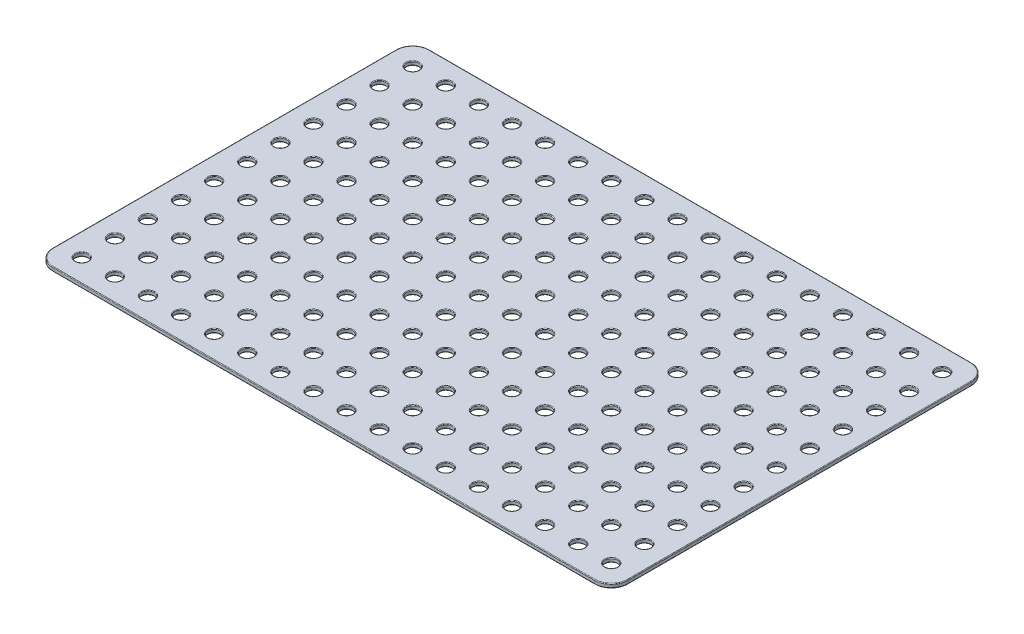
SolidWorks part; units mm, degrees
material "AISI 304"
ref_plane "Front" through (0, 0, 0) normal (0, 0, 1) x (1, 0, 0)
ref_plane "Top" through (0, 0, 0) normal (0, 1, 0) x (1, 0, 0)
ref_plane "Right" through (0, 0, 0) normal (1, 0, 0) x (0, 0, -1)
sketch "Sketch1" plane through (0, 0, 0) normal (0, 1, 0) x (1, 0, 0)
  line L1 (6.35, 0) -> (214.3252, 0)
  line L2 (0, 6.35) -> (0, 138.1252)
  line L3 (6.35, 144.4752) -> (214.3252, 144.4752)
  line L4 (220.6752, 6.35) -> (220.6752, 138.1252)
  arc A0 (0, 138.1252) -> (6.35, 144.4752) centre (6.35, 138.1252) cw
  arc A1 (6.35, 0) -> (0, 6.35) centre (6.35, 6.35) cw
  arc A2 (214.3252, 0) -> (220.6752, 6.35) centre (214.3252, 6.35) ccw
  arc A3 (214.3252, 144.4752) -> (220.6752, 138.1252) centre (214.3252, 138.1252) cw
  point P6 (0, 144.4752)
  point P9 (0, 0)
  point P14 (220.6752, 144.4752)
  dimension "D3" = 6.35
  dimension "D1" = 220.6752
  dimension "D2" = 144.4752
extrude "Extrude1" add sketch "Sketch1" along normal blind 1.524
sketch "Sketch2" plane through (0, 1.524, 0) normal (0, 1, 0) x (-1, 0, 0)
  line L0 (0, -138.1252) -> (0, -6.35) construction
  line L1 (-6.35, 0) -> (-214.3252, 0) construction
  circle A0 centre (-8.7376, -8.7376) radius 2.413
  dimension "D1" = 4.826
  dimension "D2" = 8.7376
  dimension "D3" = 8.7376
extrude "Cut-Extrude1" cut sketch "Sketch2" against normal through all
pattern_linear "LPattern1" count 17 spacing 12.7 along (1, 0, 0) count 11 spacing 12.7 along (0, 0, -1) of "Cut-Extrude1"
fillet "Fillet1" radius 0.254 390 edges at (199.2376, 0, -120.6246) (186.5376, 0, -120.6246) (173.8376, 0, -120.6246) (161.1376, 0, -120.6246) (148.4376, 0, -120.6246) (135.7376, 0, -120.6246) (123.0376, 0, -120.6246) (110.3376, 0, -120.6246) (97.6376, 0, -120.6246) (84.9376, 0, -120.6246) (72.2376, 0, -120.6246) (59.5376, 0, -120.6246) (46.8376, 0, -120.6246) (34.1376, 0, -120.6246) (21.4376, 0, -120.6246) (199.2376, 0, -107.9246) (186.5376, 0, -107.9246) (173.8376, 0, -107.9246) (161.1376, 0, -107.9246) (148.4376, 0, -107.9246) (135.7376, 0, -107.9246) (123.0376, 0, -107.9246) (110.3376, 0, -107.9246) (97.6376, 0, -107.9246) (84.9376, 0, -107.9246) (72.2376, 0, -107.9246) (59.5376, 0, -107.9246) (46.8376, 0, -107.9246) (34.1376, 0, -107.9246) (21.4376, 0, -107.9246) (199.2376, 0, -95.2246) (186.5376, 0, -95.2246) (173.8376, 0, -95.2246) (161.1376, 0, -95.2246) (148.4376, 0, -95.2246) (135.7376, 0, -95.2246) (123.0376, 0, -95.2246) (110.3376, 0, -95.2246) (97.6376, 0, -95.2246) (84.9376, 0, -95.2246) (72.2376, 0, -95.2246) (59.5376, 0, -95.2246) (46.8376, 0, -95.2246) (34.1376, 0, -95.2246) (21.4376, 0, -95.2246) (199.2376, 0, -82.5246) (186.5376, 0, -82.5246) (173.8376, 0, -82.5246) (161.1376, 0, -82.5246) (148.4376, 0, -82.5246) (135.7376, 0, -82.5246) (123.0376, 0, -82.5246) (110.3376, 0, -82.5246) (97.6376, 0, -82.5246) (84.9376, 0, -82.5246) (72.2376, 0, -82.5246) (59.5376, 0, -82.5246) (46.8376, 0, -82.5246) (34.1376, 0, -82.5246) (21.4376, 0, -82.5246) (199.2376, 0, -69.8246) (186.5376, 0, -69.8246) (173.8376, 0, -69.8246) (161.1376, 0, -69.8246) (148.4376, 0, -69.8246) (135.7376, 0, -69.8246) (123.0376, 0, -69.8246) (110.3376, 0, -69.8246) (97.6376, 0, -69.8246) (84.9376, 0, -69.8246) (72.2376, 0, -69.8246) (59.5376, 0, -69.8246) (46.8376, 0, -69.8246) (34.1376, 0, -69.8246) (21.4376, 0, -69.8246) (199.2376, 0, -57.1246) (186.5376, 0, -57.1246) (173.8376, 0, -57.1246) (161.1376, 0, -57.1246) (148.4376, 0, -57.1246) (135.7376, 0, -57.1246) (123.0376, 0, -57.1246) (110.3376, 0, -57.1246) (97.6376, 0, -57.1246) (84.9376, 0, -57.1246) (72.2376, 0, -57.1246) (59.5376, 0, -57.1246) (46.8376, 0, -57.1246) (34.1376, 0, -57.1246) (21.4376, 0, -57.1246) (199.2376, 0, -44.4246) (186.5376, 0, -44.4246) (173.8376, 0, -44.4246) (161.1376, 0, -44.4246) (148.4376, 0, -44.4246) (135.7376, 0, -44.4246) (123.0376, 0, -44.4246) (110.3376, 0, -44.4246) (97.6376, 0, -44.4246) (84.9376, 0, -44.4246) (72.2376, 0, -44.4246) (59.5376, 0, -44.4246) (46.8376, 0, -44.4246) (34.1376, 0, -44.4246) (21.4376, 0, -44.4246) (199.2376, 0, -31.7246) (186.5376, 0, -31.7246) (173.8376, 0, -31.7246) (161.1376, 0, -31.7246) (148.4376, 0, -31.7246) (135.7376, 0, -31.7246) (123.0376, 0, -31.7246) (110.3376, 0, -31.7246) (97.6376, 0, -31.7246) (84.9376, 0, -31.7246) (72.2376, 0, -31.7246) (59.5376, 0, -31.7246) (46.8376, 0, -31.7246) (34.1376, 0, -31.7246) (21.4376, 0, -31.7246) (199.2376, 0, -19.0246) (186.5376, 0, -19.0246) (173.8376, 0, -19.0246) (161.1376, 0, -19.0246) (148.4376, 0, -19.0246) (135.7376, 0, -19.0246) (123.0376, 0, -19.0246) (110.3376, 0, -19.0246) (97.6376, 0, -19.0246) (84.9376, 0, -19.0246) (72.2376, 0, -19.0246) (59.5376, 0, -19.0246) (46.8376, 0, -19.0246) (34.1376, 0, -19.0246) (0, 0, -72.2376) (1.8599, 0, -1.8599) (110.3376, 0, 0) (218.8153, 0, -1.8599) (220.6752, 0, -72.2376) (218.8153, 0, -142.6153) (110.3376, 0, -144.4752) (1.8599, 0, -142.6153) (8.7376, 0, -6.3246) (21.4376, 0, -19.0246) (8.7376, 0, -19.0246) (8.7376, 0, -31.7246) (8.7376, 0, -44.4246) (8.7376, 0, -57.1246) (8.7376, 0, -69.8246) (8.7376, 0, -82.5246) (8.7376, 0, -95.2246) (8.7376, 0, -107.9246) (8.7376, 0, -120.6246) (8.7376, 0, -133.3246) (21.4376, 0, -6.3246) (21.4376, 0, -133.3246) (34.1376, 0, -6.3246) (34.1376, 0, -133.3246) (46.8376, 0, -6.3246) (46.8376, 0, -133.3246) (59.5376, 0, -6.3246) (59.5376, 0, -133.3246) (72.2376, 0, -6.3246) (72.2376, 0, -133.3246) (84.9376, 0, -6.3246) (84.9376, 0, -133.3246) (97.6376, 0, -6.3246) (97.6376, 0, -133.3246) (110.3376, 0, -6.3246) (110.3376, 0, -133.3246) (123.0376, 0, -6.3246) (123.0376, 0, -133.3246) (135.7376, 0, -6.3246) (135.7376, 0, -133.3246) (148.4376, 0, -6.3246) (148.4376, 0, -133.3246) (161.1376, 0, -6.3246) (161.1376, 0, -133.3246) (173.8376, 0, -6.3246) (173.8376, 0, -133.3246) (186.5376, 0, -6.3246) (186.5376, 0, -133.3246) (199.2376, 0, -6.3246) (199.2376, 0, -133.3246) (211.9376, 0, -6.3246) (211.9376, 0, -19.0246) (211.9376, 0, -31.7246) (211.9376, 0, -44.4246) (211.9376, 0, -57.1246) (211.9376, 0, -69.8246) (211.9376, 0, -82.5246) (211.9376, 0, -95.2246) (211.9376, 0, -107.9246) (211.9376, 0, -120.6246) (211.9376, 0, -133.3246) (199.2376, 1.524, -120.6246) (186.5376, 1.524, -120.6246) (173.8376, 1.524, -120.6246) (161.1376, 1.524, -120.6246) (148.4376, 1.524, -120.6246) (135.7376, 1.524, -120.6246) (123.0376, 1.524, -120.6246) (110.3376, 1.524, -120.6246) (97.6376, 1.524, -120.6246) (84.9376, 1.524, -120.6246) (72.2376, 1.524, -120.6246) (59.5376, 1.524, -120.6246) (46.8376, 1.524, -120.6246) (34.1376, 1.524, -120.6246) (21.4376, 1.524, -120.6246) (199.2376, 1.524, -107.9246) (186.5376, 1.524, -107.9246) (173.8376, 1.524, -107.9246) (161.1376, 1.524, -107.9246) (148.4376, 1.524, -107.9246) (135.7376, 1.524, -107.9246) (123.0376, 1.524, -107.9246) (110.3376, 1.524, -107.9246) (97.6376, 1.524, -107.9246) (84.9376, 1.524, -107.9246) (72.2376, 1.524, -107.9246) (59.5376, 1.524, -107.9246) (46.8376, 1.524, -107.9246) (34.1376, 1.524, -107.9246) (21.4376, 1.524, -107.9246) (199.2376, 1.524, -95.2246) (186.5376, 1.524, -95.2246) (173.8376, 1.524, -95.2246) (161.1376, 1.524, -95.2246) (148.4376, 1.524, -95.2246) (135.7376, 1.524, -95.2246) (123.0376, 1.524, -95.2246) (110.3376, 1.524, -95.2246) (97.6376, 1.524, -95.2246) (84.9376, 1.524, -95.2246) (72.2376, 1.524, -95.2246) (59.5376, 1.524, -95.2246) (46.8376, 1.524, -95.2246) (34.1376, 1.524, -95.2246) (21.4376, 1.524, -95.2246) (199.2376, 1.524, -82.5246) (186.5376, 1.524, -82.5246) (173.8376, 1.524, -82.5246) (161.1376, 1.524, -82.5246) (148.4376, 1.524, -82.5246) (135.7376, 1.524, -82.5246) (123.0376, 1.524, -82.5246) (110.3376, 1.524, -82.5246) (97.6376, 1.524, -82.5246) (84.9376, 1.524, -82.5246) (72.2376, 1.524, -82.5246) (59.5376, 1.524, -82.5246) (46.8376, 1.524, -82.5246) (34.1376, 1.524, -82.5246) (21.4376, 1.524, -82.5246) (199.2376, 1.524, -69.8246) (186.5376, 1.524, -69.8246) (173.8376, 1.524, -69.8246) (161.1376, 1.524, -69.8246) (148.4376, 1.524, -69.8246) (135.7376, 1.524, -69.8246) (123.0376, 1.524, -69.8246) (110.3376, 1.524, -69.8246) (97.6376, 1.524, -69.8246) (84.9376, 1.524, -69.8246) (72.2376, 1.524, -69.8246) (59.5376, 1.524, -69.8246) (46.8376, 1.524, -69.8246) (34.1376, 1.524, -69.8246) (21.4376, 1.524, -69.8246) (199.2376, 1.524, -57.1246) (186.5376, 1.524, -57.1246) (173.8376, 1.524, -57.1246) (161.1376, 1.524, -57.1246) (148.4376, 1.524, -57.1246) (135.7376, 1.524, -57.1246) (123.0376, 1.524, -57.1246) (110.3376, 1.524, -57.1246) (97.6376, 1.524, -57.1246) (84.9376, 1.524, -57.1246) (72.2376, 1.524, -57.1246) (59.5376, 1.524, -57.1246) (46.8376, 1.524, -57.1246) (34.1376, 1.524, -57.1246) (21.4376, 1.524, -57.1246) (199.2376, 1.524, -44.4246) (186.5376, 1.524, -44.4246) (173.8376, 1.524, -44.4246) (161.1376, 1.524, -44.4246) (148.4376, 1.524, -44.4246) (135.7376, 1.524, -44.4246) (123.0376, 1.524, -44.4246) (110.3376, 1.524, -44.4246) (97.6376, 1.524, -44.4246) (84.9376, 1.524, -44.4246) (72.2376, 1.524, -44.4246) (59.5376, 1.524, -44.4246) (46.8376, 1.524, -44.4246) (34.1376, 1.524, -44.4246) (21.4376, 1.524, -44.4246) (199.2376, 1.524, -31.7246) (186.5376, 1.524, -31.7246) (173.8376, 1.524, -31.7246) (161.1376, 1.524, -31.7246) (148.4376, 1.524, -31.7246) (135.7376, 1.524, -31.7246) (123.0376, 1.524, -31.7246) (110.3376, 1.524, -31.7246) (97.6376, 1.524, -31.7246) (84.9376, 1.524, -31.7246) (72.2376, 1.524, -31.7246) (59.5376, 1.524, -31.7246) (46.8376, 1.524, -31.7246) (34.1376, 1.524, -31.7246) (21.4376, 1.524, -31.7246) (199.2376, 1.524, -19.0246) (186.5376, 1.524, -19.0246) (173.8376, 1.524, -19.0246) (161.1376, 1.524, -19.0246) (148.4376, 1.524, -19.0246) (135.7376, 1.524, -19.0246) (123.0376, 1.524, -19.0246) (110.3376, 1.524, -19.0246) (97.6376, 1.524, -19.0246) (84.9376, 1.524, -19.0246) (72.2376, 1.524, -19.0246) (59.5376, 1.524, -19.0246) (46.8376, 1.524, -19.0246) (34.1376, 1.524, -19.0246) (110.3376, 1.524, -144.4752) (218.8153, 1.524, -142.6153) (220.6752, 1.524, -72.2376) (218.8153, 1.524, -1.8599) (110.3376, 1.524, 0) (1.8599, 1.524, -1.8599) (0, 1.524, -72.2376) (1.8599, 1.524, -142.6153) (8.7376, 1.524, -6.3246) (21.4376, 1.524, -19.0246) (8.7376, 1.524, -19.0246) (8.7376, 1.524, -31.7246) (8.7376, 1.524, -44.4246) (8.7376, 1.524, -57.1246) (8.7376, 1.524, -69.8246) (8.7376, 1.524, -82.5246) (8.7376, 1.524, -95.2246) (8.7376, 1.524, -107.9246) (8.7376, 1.524, -120.6246) (8.7376, 1.524, -133.3246) (21.4376, 1.524, -6.3246) (21.4376, 1.524, -133.3246) (34.1376, 1.524, -6.3246) (34.1376, 1.524, -133.3246) (46.8376, 1.524, -6.3246) (46.8376, 1.524, -133.3246) (59.5376, 1.524, -6.3246) (59.5376, 1.524, -133.3246) (72.2376, 1.524, -6.3246) (72.2376, 1.524, -133.3246) (84.9376, 1.524, -6.3246) (84.9376, 1.524, -133.3246) (97.6376, 1.524, -6.3246) (97.6376, 1.524, -133.3246) (110.3376, 1.524, -6.3246) (110.3376, 1.524, -133.3246) (123.0376, 1.524, -6.3246) (123.0376, 1.524, -133.3246) (135.7376, 1.524, -6.3246) (135.7376, 1.524, -133.3246) (148.4376, 1.524, -6.3246) (148.4376, 1.524, -133.3246) (161.1376, 1.524, -6.3246) (161.1376, 1.524, -133.3246) (173.8376, 1.524, -6.3246) (173.8376, 1.524, -133.3246) (186.5376, 1.524, -6.3246) (186.5376, 1.524, -133.3246) (199.2376, 1.524, -6.3246) (199.2376, 1.524, -133.3246) (211.9376, 1.524, -6.3246) (211.9376, 1.524, -19.0246) (211.9376, 1.524, -31.7246) (211.9376, 1.524, -44.4246) (211.9376, 1.524, -57.1246) (211.9376, 1.524, -69.8246) (211.9376, 1.524, -82.5246) (211.9376, 1.524, -95.2246) (211.9376, 1.524, -107.9246) (211.9376, 1.524, -120.6246) (211.9376, 1.524, -133.3246)
